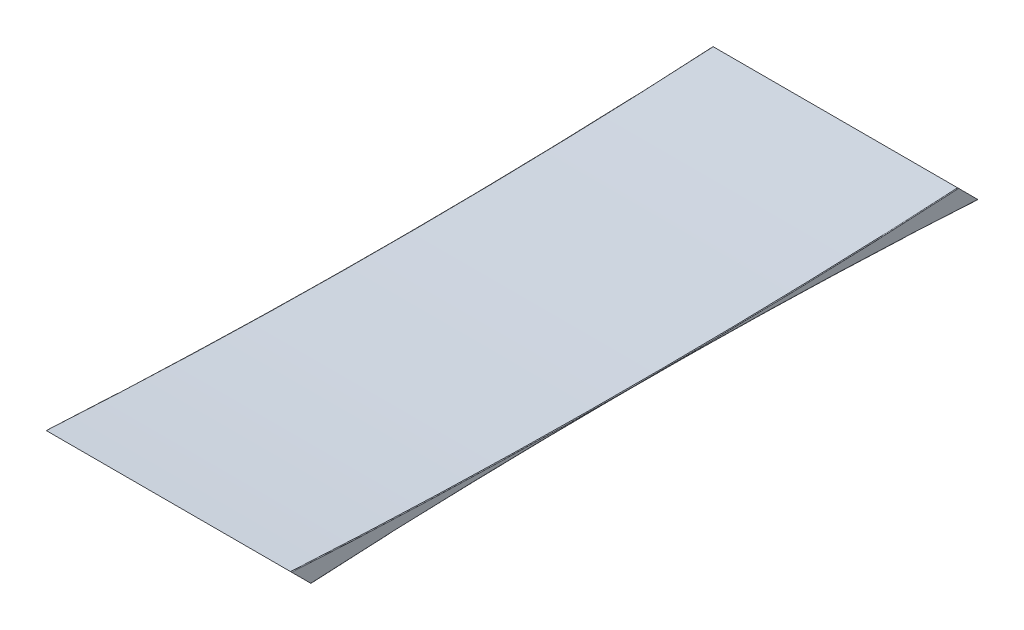
SolidWorks part; units mm, degrees
ref_plane "Front Plane" through (0, 0, 0) normal (0, 0, 1) x (1, 0, 0)
ref_plane "Top Plane" through (0, 0, 0) normal (0, 1, 0) x (1, 0, 0)
ref_plane "Right Plane" through (0, 0, 0) normal (1, 0, 0) x (0, 0, -1)
sketch "Sketch1" plane through (0, 0, 0) normal (0, 1, 0) x (1, 0, 0)
  line L0 (-1, 0) -> (1, 0) construction
  line L1 (-1, 2.8) -> (1, 2.8)
  line L2 (-1, 2.8) -> (-1, -2.8)
  line L3 (-1, -2.8) -> (1, -2.8)
  line L4 (1, 2.8) -> (1, -2.8)
  line L5 (-1, 2.8) -> (1, -2.8) construction
  line L6 (-1, -2.8) -> (1, 2.8) construction
  point P0 (0, 0)
  dimension "D1" = 2
  dimension "D2" = 2.8
extrude "Boss-Extrude1" add sketch "Sketch1" along normal mid plane 0.174
sketch "Sketch3" plane through (-1, 0, 0) normal (-1, 0, 0) x (0, 0, 1)
  line L0 (0, 0.005) -> (0, -0.005) construction
  line L1 (-2.8, 0.087) -> (2.8, 0.087)
  line L2 (-2.8, -0.087) -> (2.8, -0.087)
  arc A0 (-2.8, 0.087) -> (2.8, 0.087) centre (0, 47.8509) ccw
  arc A1 (-2.8, -0.087) -> (2.8, -0.087) centre (0, -47.8509) cw
  point P2 (0, 0)
  dimension "D1" = 0.01
extrude "Cut-Extrude1" cut sketch "Sketch3" against normal through all
sketch "Sketch4" plane through (-1, 0, 0) normal (-1, 0, 0) x (0, 0, 1)
  line L0 (2.8, 0.087) -> (2.626, -0.087)
  line L1 (2.8, -0.087) -> (2.626, -0.087)
  line L2 (2.8, 0.087) -> (2.8, -0.087)
  line L3 (-2.8, -0.087) -> (-2.626, 0.087)
  line L4 (-2.626, 0.087) -> (-2.8, 0.087)
  line L5 (-2.8, 0.087) -> (-2.8, -0.087)
  dimension "D1" = 45
  dimension "D2" = 45
extrude "Cut-Extrude2" cut sketch "Sketch4" against normal through all
fillet "Fillet1" radius 0.005 4 edges at (1, -0.0051, -0.0824) (1, 0.0051, 0.0824) (-1, -0.0051, -0.0824) (-1, 0.0051, 0.0824)
ref_plane "Plane1" through (0, 0, 0) normal (0, -0.7071, 0.7071) x (1, 0, 0)
ref_plane "Plane2" through (0, 0, 0) normal (0, 0.7071, 0.7071) x (1, 0, 0)
